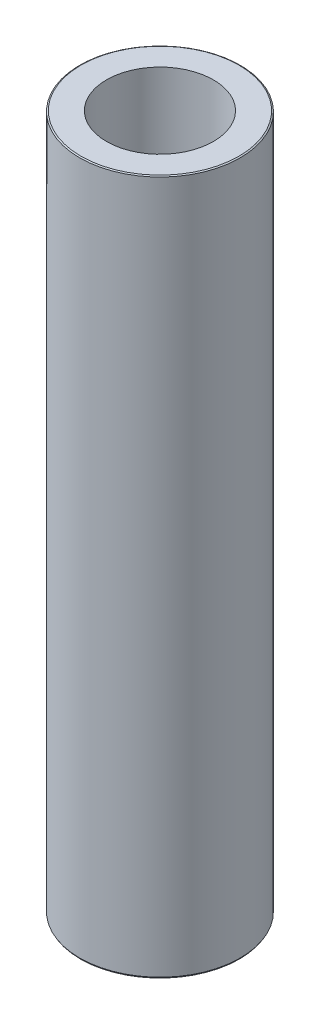
SolidWorks part; units mm, degrees
ref_plane "Front Plane" through (0, 0, 0) normal (0, 0, 1) x (1, 0, 0)
ref_plane "Top Plane" through (0, 0, 0) normal (0, 1, 0) x (1, 0, 0)
ref_plane "Right Plane" through (0, 0, 0) normal (1, 0, 0) x (0, 0, -1)
sketch "Sketch1" plane through (0, 0, 0) normal (0, 1, 0) x (1, 0, 0)
  circle A0 centre (0, 0) radius 22.5
  dimension "SHAFT_OD" = 45
extrude "Boss-Extrude1" add sketch "Sketch1" along normal blind 194.8579
sketch "Sketch2" plane through (0, 0, 0) normal (0, 1, 0) x (1, 0, 0)
  circle A0 centre (0, 0) radius 14.9881
  dimension "BORE_D" = 29.9762
extrude "Cut-Extrude1" cut sketch "Sketch2" along normal through all
chamfer "Chamfer1" distance 0.2081 angle 60 2 edges at (0, 194.8579, 22.5) (0, 0, 22.5) first distance on face at (0, 194.8579, 22.5) first distance on face at (0, 0, 14.9881)
